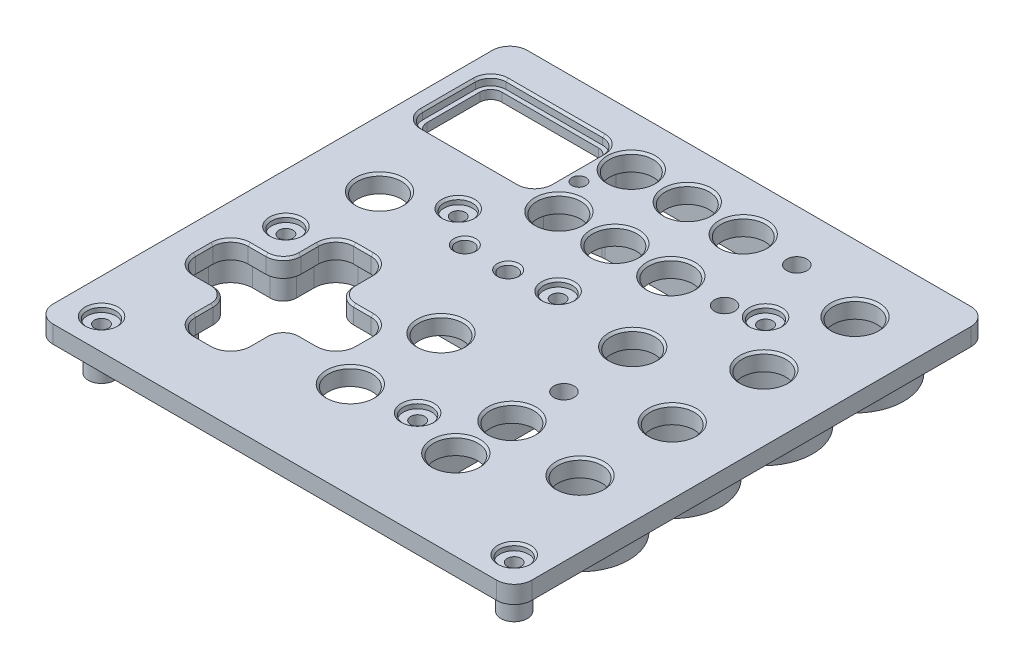
SolidWorks part; units mm, degrees
other "Markup1"
sketch "Sketch10" plane through (-33.0518, -8.9554, -52.6589) normal (-0.1076, -0.9941, -0.0133) x (0.4564, -0.0613, 0.8876)
ref_plane "Front Plane" through (0, 0, 0) normal (0, 0, 1) x (1, 0, 0)
ref_plane "Top Plane" through (0, 0, 0) normal (0, 1, 0) x (1, 0, 0)
ref_plane "Right Plane" through (0, 0, 0) normal (1, 0, 0) x (0, 0, -1)
sketch "Sketch1" plane through (0, 0, 0) normal (0, 1, 0) x (1, 0, 0)
  line L0 (32.6312, 56.5) -> (133.6312, 56.5)
  line L7 (137.6312, -47.5) -> (137.6312, 52.5)
  line L28 (28.6312, 52.5) -> (28.6312, -47.5)
  line L30 (32.6312, -51.5) -> (133.6312, -51.5)
  arc A0 (28.6312, -47.5) -> (32.6312, -51.5) centre (32.6312, -47.5) ccw
  arc A1 (133.6312, -51.5) -> (137.6312, -47.5) centre (133.6312, -47.5) ccw
  arc A2 (137.6312, 52.5) -> (133.6312, 56.5) centre (133.6312, 52.5) ccw
  arc A3 (32.6312, 56.5) -> (28.6312, 52.5) centre (32.6312, 52.5) ccw
  dimension "D2" = 4
extrude "Boss-Extrude1" add sketch "Sketch1" along normal blind 4
sketch "Sketch3" plane through (0, 4, 0) normal (0, 1, 0) x (1, 0, 0)
  line L44 (50.9951, -1.4499) -> (54.9951, -1.4499)
  line L45 (58.9951, -5.4499) -> (58.9951, -9.4499)
  line L46 (62.9951, -13.4499) -> (66.9951, -13.4499)
  line L47 (70.9951, -17.4499) -> (70.9951, -21.4499)
  line L48 (66.9951, -25.4499) -> (62.9951, -25.4499)
  line L49 (58.9951, -29.4499) -> (58.9951, -33.4499)
  line L50 (54.9951, -37.4499) -> (50.9951, -37.4499)
  line L51 (46.9951, -33.4499) -> (46.9951, -29.4499)
  line L52 (42.9951, -25.4499) -> (38.9951, -25.4499)
  line L53 (34.9951, -21.4499) -> (34.9951, -17.4499)
  line L54 (38.9951, -13.4499) -> (42.9951, -13.4499)
  line L55 (46.9951, -9.4499) -> (46.9951, -5.4499)
  circle A2 centre (122.5061, 41.25) radius 5
  circle A3 centre (122.5061, 20.5) radius 5
  circle A4 centre (122.5061, -0.375) radius 5
  circle A5 centre (122.5061, -21.375) radius 5
  circle A6 centre (103.9561, -18.35) radius 5
  circle A7 centre (103.1311, 10) radius 5
  circle A8 centre (78.5811, -9.125) radius 5
  circle A9 centre (78.3063, -29.5) radius 5
  circle A10 centre (43.6312, 11.8249) radius 5
  circle A11 centre (68.0062, 28.3001) radius 5
  circle A12 centre (80.7562, 28.3001) radius 5
  circle A13 centre (93.5062, 28.3001) radius 5
  circle A14 centre (93.5062, 44.8001) radius 5
  circle A15 centre (80.7562, 44.8001) radius 5
  circle A16 centre (68.0062, 44.8001) radius 5
  circle A17 centre (103.9561, -31.125) radius 5
  circle A18 centre (63.8812, 11.0001) radius 2
  circle A19 centre (73.7562, 10.9999) radius 2
  arc A20 (58.9951, -29.4499) -> (62.9951, -25.4499) centre (62.9951, -29.4499) cw
  arc A21 (62.9951, -13.4499) -> (58.9951, -9.4499) centre (62.9951, -9.4499) cw
  arc A22 (46.9951, -9.4499) -> (42.9951, -13.4499) centre (42.9951, -9.4499) cw
  arc A23 (46.9951, -29.4499) -> (42.9951, -25.4499) centre (42.9951, -29.4499) ccw
  arc A24 (70.9951, -17.4499) -> (66.9951, -13.4499) centre (66.9951, -17.4499) ccw
  arc A25 (58.9951, -5.4499) -> (54.9951, -1.4499) centre (54.9951, -5.4499) ccw
  arc A26 (50.9951, -1.4499) -> (46.9951, -5.4499) centre (50.9951, -5.4499) ccw
  arc A27 (38.9951, -13.4499) -> (34.9951, -17.4499) centre (38.9951, -17.4499) ccw
  arc A28 (34.9951, -21.4499) -> (38.9951, -25.4499) centre (38.9951, -21.4499) ccw
  arc A29 (46.9951, -33.4499) -> (50.9951, -37.4499) centre (50.9951, -33.4499) ccw
  arc A30 (54.9951, -37.4499) -> (58.9951, -33.4499) centre (54.9951, -33.4499) ccw
  arc A31 (66.9951, -25.4499) -> (70.9951, -21.4499) centre (66.9951, -21.4499) ccw
  circle A32 centre (105.6344, 44.8749) radius 2.3
  circle A33 centre (105.4147, 28.6249) radius 2.3
  circle A34 centre (104.1313, -6.6735) radius 2.3
  point P54 (58.9951, -13.4499)
extrude "Cut-Extrude2" cut sketch "Sketch3" against normal through all
sketch "Sketch11" plane through (0, 4, 0) normal (0, 1, 0) x (1, 0, 0)
  line L0 (61.4355, 44.8615) -> (61.4355, 32.8615)
  line L4 (32.4355, 32.8615) -> (32.4355, 44.8615)
  line L6 (35.9355, 48.3615) -> (57.9355, 48.3615)
  line L8 (61.4355, 44.8615) -> (61.4355, 32.8615)
  line L9 (57.9355, 29.3615) -> (35.9355, 29.3615)
  line L10 (32.4355, 32.8615) -> (32.4355, 44.8615)
  line L11 (35.9355, 48.3615) -> (57.9355, 48.3615)
  line L13 (57.9355, 29.3615) -> (35.9355, 29.3615)
  arc A0 (57.9355, 29.3615) -> (61.4355, 32.8615) centre (57.9355, 32.8615) ccw
  arc A1 (32.4355, 32.8615) -> (35.9355, 29.3615) centre (35.9355, 32.8615) ccw
  arc A2 (35.9355, 48.3615) -> (32.4355, 44.8615) centre (35.9355, 44.8615) ccw
  arc A3 (61.4355, 44.8615) -> (57.9355, 48.3615) centre (57.9355, 44.8615) ccw
  arc A4 (57.9355, 29.3615) -> (61.4355, 32.8615) centre (57.9355, 32.8615) ccw
  arc A5 (32.4355, 32.8615) -> (35.9355, 29.3615) centre (35.9355, 32.8615) ccw
  arc A6 (35.9355, 48.3615) -> (32.4355, 44.8615) centre (35.9355, 44.8615) ccw
  arc A7 (61.4355, 44.8615) -> (57.9355, 48.3615) centre (57.9355, 44.8615) ccw
extrude "Cut-Extrude8" cut sketch "Sketch11" against normal blind 2
sketch "Sketch12" plane through (0, 2, 0) normal (0, 1, 0) x (1, 0, 0)
  line L4 (57.9355, 47.3615) -> (35.9355, 47.3615)
  line L5 (57.9355, 47.3615) -> (35.9355, 47.3615)
  line L6 (33.4355, 44.8615) -> (33.4355, 32.8615)
  line L7 (33.4355, 44.8615) -> (33.4355, 32.8615)
  line L8 (35.9355, 30.3615) -> (57.9355, 30.3615)
  line L9 (35.9355, 30.3615) -> (57.9355, 30.3615)
  line L10 (60.4355, 32.8615) -> (60.4355, 44.8615)
  line L11 (60.4355, 32.8615) -> (60.4355, 44.8615)
  arc A4 (60.4355, 44.8615) -> (57.9355, 47.3615) centre (57.9355, 44.8615) ccw
  arc A5 (60.4355, 44.8615) -> (57.9355, 47.3615) centre (57.9355, 44.8615) ccw
  arc A6 (35.9355, 47.3615) -> (33.4355, 44.8615) centre (35.9355, 44.8615) ccw
  arc A7 (35.9355, 47.3615) -> (33.4355, 44.8615) centre (35.9355, 44.8615) ccw
  arc A8 (33.4355, 32.8615) -> (35.9355, 30.3615) centre (35.9355, 32.8615) ccw
  arc A9 (33.4355, 32.8615) -> (35.9355, 30.3615) centre (35.9355, 32.8615) ccw
  arc A10 (57.9355, 30.3615) -> (60.4355, 32.8615) centre (57.9355, 32.8615) ccw
  arc A11 (57.9355, 30.3615) -> (60.4355, 32.8615) centre (57.9355, 32.8615) ccw
  dimension "D1" = 1
extrude "Cut-Extrude9" cut sketch "Sketch12" against normal through all
sketch "Sketch13" plane through (0, 0, 0) normal (0, -1, 0) x (1, 0, 0)
  line L0 (133.6312, -52.5) -> (28.6312, -52.5) construction
  line L2 (112.3813, -52.5) -> (112.3813, -45.8324)
  line L4 (61.3813, -52.5) -> (61.3813, -21.5)
  line L5 (68.0062, -22.3001) -> (106.5062, -22.3001)
  line L7 (68.0062, -51.3001) -> (106.5062, -51.3001)
  line L8 (110.5062, -47.3001) -> (110.5062, -42.8001)
  line L10 (68.0062, -38.8001) -> (106.5062, -38.8001)
  line L12 (110.5062, -34.3001) -> (110.5062, -26.3001)
  line L14 (92.0062, -10.073) -> (92.0062, -16.5)
  line L16 (96.9561, 31.125) -> (96.9561, 6.3677)
  line L17 (110.9561, 6.3677) -> (110.9561, 31.125)
  line L18 (94.9561, 31.125) -> (94.9561, 6.3677)
  line L20 (112.9561, 27.1103) -> (112.9561, 31.125)
  line L22 (112.9561, 6.3677) -> (112.9561, 31.125) construction
  line L58 (49.0951, -3.4501) -> (56.6951, -3.4501)
  line L64 (51.4145, 42.1499) -> (49.0951, 42.1499)
  line L65 (42.0951, 35.1499) -> (42.0951, 31.1499)
  line L66 (41.0951, 30.1499) -> (37.0951, 30.1499)
  line L67 (30.0951, 23.1499) -> (30.0951, 15.5499)
  line L68 (37.0951, 8.5499) -> (41.0951, 8.5499)
  line L69 (42.0951, 7.5499) -> (42.0951, 3.5499)
  line L78 (87, 41.2148) -> (87, 1.6203)
  line L80 (87, 41.2148) -> (81.1395, 41.2148)
  line L90 (80.1354, -3.1952) -> (60.3806, -3.1952)
  line L91 (60.3806, -3.1952) -> (56.6951, -3.4501)
  line L92 (81.1395, 41.2148) -> (80.9453, 41.2148)
  line L98 (78.4256, -1.1952) -> (60.3115, -1.1952)
  line L99 (60.3115, -1.1952) -> (56.626, -1.4501)
  line L100 (49.0951, -1.4501) -> (56.626, -1.4501)
  line L101 (44.0951, 7.5499) -> (44.0951, 3.5499)
  line L102 (37.0951, 10.5499) -> (41.0951, 10.5499)
  line L103 (32.0951, 23.1499) -> (32.0951, 15.5499)
  line L104 (41.0951, 28.1499) -> (37.0951, 28.1499)
  line L105 (44.0951, 35.1499) -> (44.0951, 31.1499)
  line L106 (56.6951, 40.1499) -> (49.0951, 40.1499)
  line L112 (88.0062, -20.5) -> (61.3813, -20.5)
  line L113 (61.3813, -20.5) -> (61.3813, -21.5)
  line L114 (110.5062, -34.3001) -> (110.5062, -35.3001)
  line L115 (110.5062, -35.3001) -> (71.526, -35.3001)
  line L117 (72.1395, 36.8974) -> (59.4553, 39.319) construction
  line L118 (81.8089, 36.8974) -> (72.1395, 36.8974) construction
  line L119 (72.3287, 38.8974) -> (60.1904, 41.2148) construction
  line L120 (79.8089, 38.8974) -> (72.3287, 38.8974) construction
  line L122 (85, 39.2148) -> (85, 0.6001) construction
  line L123 (85, 39.2148) -> (81.8089, 39.2148) construction
  line L124 (81.8089, 39.2148) -> (81.8089, 36.8974) construction
  line L126 (81.8089, 39.2148) -> (81.8089, 39.2148) construction
  line L127 (85, 0.6001) -> (78.6937, 0.6001) construction
  line L128 (85, 0.6001) -> (85, 0.6001) construction
  line L129 (85, 4.6001) -> (85, 35.9119)
  line L130 (85, 4.6001) -> (85, 4.3183)
  line L135 (61.3813, -52.5) -> (112.3813, -52.5)
  line L136 (56.6951, 42.1499) -> (49.0951, 42.1499) construction
  line L137 (81.7885, 39.1911) -> (60.1254, 39.1911)
  line L138 (79.8089, 41.2148) -> (79.8089, 38.8974) construction
  line L139 (60.7768, 41.1028) -> (72.9994, 41.1028)
  line L143 (81.1395, 41.2148) -> (79.8089, 41.2148) construction
  line L144 (81.2306, -3.0424) -> (84.0953, -2.2268)
  line L145 (82.4501, -0.032) -> (82.3087, -0.1438)
  line L146 (80.3612, -0.9707) -> (78.9594, -1.1595)
  line L147 (78.6937, -1.1952) -> (60.3115, -1.1952) construction
  line L148 (78.6937, 0.6001) -> (78.6937, -1.1952) construction
  line L149 (85.6449, -1.3999) -> (80.6937, -1.3999) construction
  line L150 (87, -1.3999) -> (85.6449, -1.3999) construction
  line L151 (80.6937, -1.3999) -> (80.6937, -3.1952) construction
  line L152 (80.6937, -3.1952) -> (60.3806, -3.1952) construction
  line L153 (87, 41.2148) -> (87, -1.3999) construction
  line L154 (68.272, -34.8415) -> (70.9104, -35.2525)
  arc A5 (68.0062, -38.8001) -> (62.3939, -46.9221) centre (68.0062, -44.8001) ccw
  arc A7 (68.0062, -51.3001) -> (62.3939, -46.9221) centre (68.0062, -45.5139) cw
  circle A8 centre (122.5061, -41.25) radius 10
  circle A9 centre (122.5061, -20.5) radius 10
  circle A10 centre (122.5061, 0.4032) radius 10
  circle A11 centre (103.1311, -10) radius 10
  circle A12 centre (122.5061, 21.375) radius 10
  arc A15 (130.5136, 13.6805) -> (112.9561, 27.1103) centre (122.506, 21.4035) ccw
  arc A16 (105.5959, 0.8487) -> (101.7697, 1.0416) centre (103.1311, -10) ccw
  arc A20 (130.5579, -7.2742) -> (130.5137, 8.1268) centre (122.5061, 0.4032) ccw
  arc A21 (130.6014, -28.1033) -> (130.5579, -12.7949) centre (122.5062, -20.4721) ccw
  arc A25 (112.3813, -45.8324) -> (130.6014, -33.5908) centre (122.5062, -41.2221) ccw
  arc A26 (110.9561, 31.125) -> (96.9561, 31.125) centre (103.9561, 31.125) ccw
  arc A28 (96.9561, 6.3677) -> (97.7122, 3.2032) centre (103.9561, 6.3677) ccw
  arc A29 (112.9561, 31.125) -> (94.9561, 31.125) centre (103.9561, 31.125) ccw
  arc A30 (94.9561, 6.3677) -> (95.8988, 2.3578) centre (103.9561, 6.3677) ccw
  arc A34 (109.8501, 2.5914) -> (110.9561, 6.3677) centre (103.9561, 6.3677) ccw
  arc A35 (94.9561, 6.3677) -> (112.9561, 6.3677) centre (103.9561, 6.3677) ccw construction
  arc A36 (95.1775, -2.2212) -> (92.0062, -10.073) centre (103.1311, -10) ccw
  arc A37 (96.9561, 6.3677) -> (110.9561, 6.3677) centre (103.9561, 6.3677) ccw construction
  arc A76 (42.0951, 3.5499) -> (49.0951, -3.4501) centre (49.0951, 3.5499) ccw
  arc A82 (59.7699, 41.4384) -> (56.6951, 42.1499) centre (56.6951, 35.1499) ccw
  arc A83 (49.0951, 42.1499) -> (42.0951, 35.1499) centre (49.0951, 35.1499) ccw
  arc A84 (41.0951, 30.1499) -> (42.0951, 31.1499) centre (41.0951, 31.1499) ccw
  arc A85 (37.0951, 30.1499) -> (30.0951, 23.1499) centre (37.0951, 23.1499) ccw
  arc A86 (30.0951, 15.5499) -> (37.0951, 8.5499) centre (37.0951, 15.5499) ccw
  arc A87 (42.0951, 7.5499) -> (41.0951, 8.5499) centre (41.0951, 7.5499) ccw
  arc A90 (44.0951, 3.5499) -> (49.0951, -1.4501) centre (49.0951, 3.5499) ccw
  arc A91 (44.0951, 7.5499) -> (41.0951, 10.5499) centre (41.0951, 7.5499) ccw
  arc A92 (32.0951, 15.5499) -> (37.0951, 10.5499) centre (37.0951, 15.5499) ccw
  arc A93 (37.0951, 28.1499) -> (32.0951, 23.1499) centre (37.0951, 23.1499) ccw
  arc A94 (41.0951, 28.1499) -> (44.0951, 31.1499) centre (41.0951, 31.1499) ccw
  arc A95 (49.0951, 40.1499) -> (44.0951, 35.1499) centre (49.0951, 35.1499) ccw
  arc A96 (59.0175, 39.5778) -> (56.6951, 40.1499) centre (56.6951, 35.1499) ccw
  arc A97 (88.0062, -20.5) -> (92.0062, -16.5) centre (88.0062, -16.5) ccw
  arc A98 (130.5136, 13.6805) -> (130.5137, 8.1268) centre (133.3928, 10.9037) ccw
  arc A99 (130.6014, -28.1033) -> (130.6014, -33.5908) centre (133.512, -30.8471) ccw
  arc A100 (130.5579, -7.2742) -> (130.5579, -12.7949) centre (133.4528, -10.0346) ccw
  arc A101 (105.5959, 0.8487) -> (109.8501, 2.5914) centre (106.4821, 4.7493) ccw
  arc A102 (101.7697, 1.0416) -> (97.7122, 3.2032) centre (101.2802, 5.0115) cw
  arc A103 (106.5062, -51.3001) -> (110.5062, -47.3001) centre (106.5062, -47.3001) ccw
  arc A104 (106.5062, -38.8001) -> (110.5062, -42.8001) centre (106.5062, -42.8001) cw
  arc A105 (106.5062, -22.3001) -> (110.5062, -26.3001) centre (106.5062, -26.3001) cw
  arc A107 (59.4553, 39.319) -> (56.6951, 40.1499) centre (56.6951, 35.1499) ccw construction
  arc A108 (59.0175, 39.5778) -> (60.1254, 39.1911) centre (60.8755, 43.1201) ccw
  arc A109 (60.1904, 41.2148) -> (56.6951, 42.1499) centre (56.6951, 35.1499) ccw construction
  arc A110 (59.7699, 41.4384) -> (60.7768, 41.1028) centre (61.527, 45.0318) ccw
  arc A112 (95.8988, 2.3578) -> (95.1775, -2.2212) centre (92.3178, 0.5756) cw
  arc A113 (85, 35.9119) -> (81.7885, 39.1911) centre (83.5458, 37.6999) ccw
  arc A115 (83.8131, 0.6711) -> (85.1693, 3.167) centre (83.2539, 2.5914) ccw
  arc A116 (85.1693, 3.167) -> (85, 4.3183) centre (89, 4.3183) cw
  arc A117 (56.6951, 42.1499) -> (55.6799, 42.0189) centre (56.6951, 38.1499) ccw
  arc A118 (51.4145, 42.1499) -> (52.8417, 41.8866) centre (51.4145, 38.1499) cw
  arc A119 (52.8417, 41.8866) -> (55.6799, 42.0189) centre (54.1092, 45.2051) ccw
  arc A120 (74.7448, 40.7019) -> (72.9994, 41.1028) centre (72.9994, 37.1028) ccw
  arc A121 (74.7448, 40.7019) -> (79.0991, 40.7632) centre (76.8609, 45.0653) ccw
  arc A122 (80.9453, 41.2148) -> (79.0991, 40.7632) centre (80.9453, 37.2148) ccw
  arc A123 (78.9594, -1.1595) -> (78.4256, -1.1952) centre (78.4256, 2.8048) cw
  arc A124 (82.3087, -0.1438) -> (80.3612, -0.9707) centre (79.8274, 2.9935) cw
  arc A125 (83.8131, 0.6711) -> (82.4501, -0.032) centre (84.9315, -3.1693) ccw
  arc A126 (81.2306, -3.0424) -> (80.1354, -3.1952) centre (80.1354, 0.8048) cw
  arc A127 (87, 1.6203) -> (84.0953, -2.2268) centre (83, 1.6203) cw
  arc A128 (67.7993, -34.7964) -> (62.3939, -30.4221) centre (68.0062, -29.0139) cw
  arc A129 (68.0062, -22.3001) -> (62.3939, -30.4221) centre (68.0062, -28.3001) ccw
  arc A130 (71.526, -35.3001) -> (70.9104, -35.2525) centre (71.526, -31.3001) cw
  arc A131 (68.272, -34.8415) -> (67.7993, -34.7964) centre (67.6564, -38.7939) ccw
  point P139 (56.6951, 3.5499)
  point P140 (63.6951, 3.5499)
  point P144 (68.6951, 8.5499)
  point P145 (68.6951, 15.5499)
  point P146 (75.6951, 15.5499)
  point P153 (63.6951, 35.1499)
  dimension "D3" = 4
  dimension "D1" = 4
  dimension "D4" = 4
  dimension "D5" = 4
  dimension "D6" = 4
  dimension "D7" = 4
  dimension "D8" = 4
  dimension "D9" = 4
  dimension "D10" = 4
  dimension "D11" = 4
  dimension "D12" = 4
  dimension "D13" = 4
  dimension "D14" = 4
  dimension "D15" = 4
  dimension "D16" = 4
  dimension "D17" = 4
  dimension "D2" = 51
extrude "Boss-Extrude2" add sketch "Sketch13" along normal blind 7.1
sketch "Sketch14" plane through (0, -7.1, 0) normal (0, -1, 0) x (1, 0, 0)
  line L0 (110.9561, 31.125) -> (110.9561, 40.2144)
  line L5 (110.9561, 40.2144) -> (106.9561, 40.2144)
  line L7 (106.9561, 31.125) -> (110.9561, 31.125)
  line L8 (106.9561, 31.125) -> (96.9561, 31.125)
  line L9 (96.9561, 31.125) -> (96.9561, 40.2144)
  line L10 (96.9561, 40.2144) -> (106.9561, 40.2144)
extrude "Cut-Extrude10" cut sketch "Sketch14" against normal blind 1.5
sketch "Sketch8" plane through (0, 4, 0) normal (0, -1, 0) x (-1, 0, 0)
  circle A0 centre (-36.6312, -44.5) radius 1.6
  circle A1 centre (-91.6312, -27.5) radius 1.6
  circle A2 centre (-39.8812, -5.75) radius 1.6
  circle A3 centre (-56.0062, 17.375) radius 1.6
  circle A4 centre (-64.3812, 36.5) radius 1.6
  circle A5 centre (-83.6312, 12.5) radius 1.6
  circle A6 centre (-112.3812, 31) radius 1.6
  circle A7 centre (-130.6312, -44.5) radius 1.6
extrude "Cut-Extrude7" cut sketch "Sketch8" along normal through all
sketch "Sketch16" plane through (0, 0, 0) normal (0, -1, 0) x (1, 0, 0)
  line L1 (37.0951, 8.5499) -> (41.0951, 8.5499) construction
  line L3 (40.9586, 8.5499) -> (41.0951, 8.5499)
  line L4 (87, 1.6203) -> (87, 41.2148) construction
  line L5 (94.9561, 31.125) -> (94.9561, 6.3677) construction
  line L6 (87, 24.5) -> (87, 30.5)
  line L7 (94.9561, 30.5) -> (94.9561, 24.5)
  line L8 (91.6312, 24.5) -> (87, 24.5)
  line L9 (91.6312, 30.5) -> (87, 30.5)
  line L10 (91.6312, 30.5) -> (94.9561, 30.5)
  line L11 (91.6312, 24.5) -> (94.9561, 24.5)
  circle A0 centre (36.6312, 44.5) radius 3
  arc A1 (40.9586, 8.5499) -> (42.0601, 7.8121) centre (39.8812, 5.75) ccw
  circle A2 centre (56.0062, -17.375) radius 3
  circle A4 centre (130.6312, 44.5) radius 3
  circle A5 centre (83.6312, -12.5) radius 3
  arc A6 (42.0951, 7.5499) -> (41.0951, 8.5499) centre (41.0951, 7.5499) ccw construction
  arc A7 (42.0601, 7.8121) -> (41.0951, 8.5499) centre (41.0951, 7.5499) ccw
fillet "Fillet1" radius 4 1 edges at (110.5062, -3.55, -35.3001)
fillet "Fillet2" radius 4 1 edges at (112.9561, -3.55, 27.1103)
fillet "Fillet5" radius 4 1 edges at (112.3813, -3.55, -45.8324)
sketch "Sketch15" plane through (0, 4, 0) normal (0, 1, 0) x (1, 0, 0)
  circle A0 centre (56.0062, 17.375) radius 3.25
  circle A1 centre (39.8812, -5.75) radius 3.25
  circle A2 centre (36.6312, -44.5) radius 3.25
  circle A3 centre (91.6312, -27.5) radius 3.25
  circle A4 centre (130.6312, -44.5) radius 3.25
  circle A5 centre (112.3812, 31) radius 3.25
  circle A6 centre (83.6312, 12.5) radius 3.25
extrude "Cut-Extrude11" cut sketch "Sketch15" against normal blind 1.5
chamfer "Chamfer1" distance 0.5 angle 45 57 edges at (93.5062, 4, -39.8001) (80.7562, 4, -39.8001) (68.0062, 4, -39.8001) (63.8812, 4, -9.0001) (73.7562, 4, -8.9999) (83.6312, 4, -9.25) (56.0062, 4, -14.125) (43.6312, 4, -6.8249) (39.8812, 4, 9) (36.6312, 4, 47.75) (52.9951, 4, 37.4499) (46.9951, 4, 31.4499) (45.8235, 4, 26.6215) (40.9951, 4, 25.4499) (34.9951, 4, 19.4499) (40.9951, 4, 13.4499) (45.8235, 4, 12.2783) (46.9951, 4, 7.4499) (52.9951, 4, 1.4499) (58.9951, 4, 31.4499) (58.9951, 4, 7.4499) (60.1667, 4, 26.6215) (60.1667, 4, 12.2783) (64.9951, 4, 25.4499) (70.9951, 4, 19.4499) (64.9951, 4, 13.4499) (78.5811, 4, 14.125) (78.3063, 4, 34.5) (130.6312, 4, 47.75) (91.6312, 4, 30.75) (103.9561, 4, 36.125) (103.9561, 4, 23.35) (122.5061, 4, 26.375) (122.5061, 4, 5.375) (103.1311, 4, -5) (122.5061, 4, -15.5) (112.3812, 4, -27.75) (93.5062, 4, -23.3001) (80.7562, 4, -23.3001) (68.0062, 4, -23.3001) (32.4355, 4, -38.8615) (61.4355, 4, -38.8615) (46.9355, 4, -29.3615) (60.4103, 4, -30.3866) (33.4606, 4, -30.3866) (60.4103, 4, -47.3364) (33.4606, 4, -47.3364) (46.9355, 4, -48.3615) (122.5061, 4, -36.25) (36.1667, 4, 24.2783) (48.1667, 4, 36.2783) (36.1667, 4, 14.6215) (57.8235, 4, 36.2783) (48.1667, 4, 2.6215) (69.8235, 4, 24.2783) (57.8235, 4, 2.6215) (69.8235, 4, 14.6215)
fillet "Fillet10" radius 3 1 edges at (87, -3.55, 41.2148)
extrude "Boss-Extrude4" add sketch "Sketch16" along normal up to surface (7.1 mm away) up to face at (112.3812, -7.1, -32.6)
sketch "Sketch17" plane through (0, 0, 0) normal (0, 1, 0) x (1, 0, 0)
  circle A0 centre (36.6312, -44.5) radius 1.6
  circle A1 centre (39.8812, -5.75) radius 1.6
  circle A2 centre (56.0062, 17.375) radius 1.6
  circle A3 centre (83.6312, 12.5) radius 1.6
  circle A4 centre (91.6312, -27.5) radius 1.6
  circle A6 centre (130.6312, -44.5) radius 1.6
extrude "Cut-Extrude12" cut sketch "Sketch17" against normal through all
fillet "Fillet13" radius 2 9 edges at (94.9561, -3.55, 30.5) (87, -3.55, 30.5) (94.9561, -3.55, 24.5) (87, -3.55, 24.5) (38.8039, -3.55, 8.5499) (42.0951, -3.55, 3.7255) (61.3813, -3.55, -20.5) (112.3813, -3.55, -52.5) (61.3813, -3.55, -52.5)
